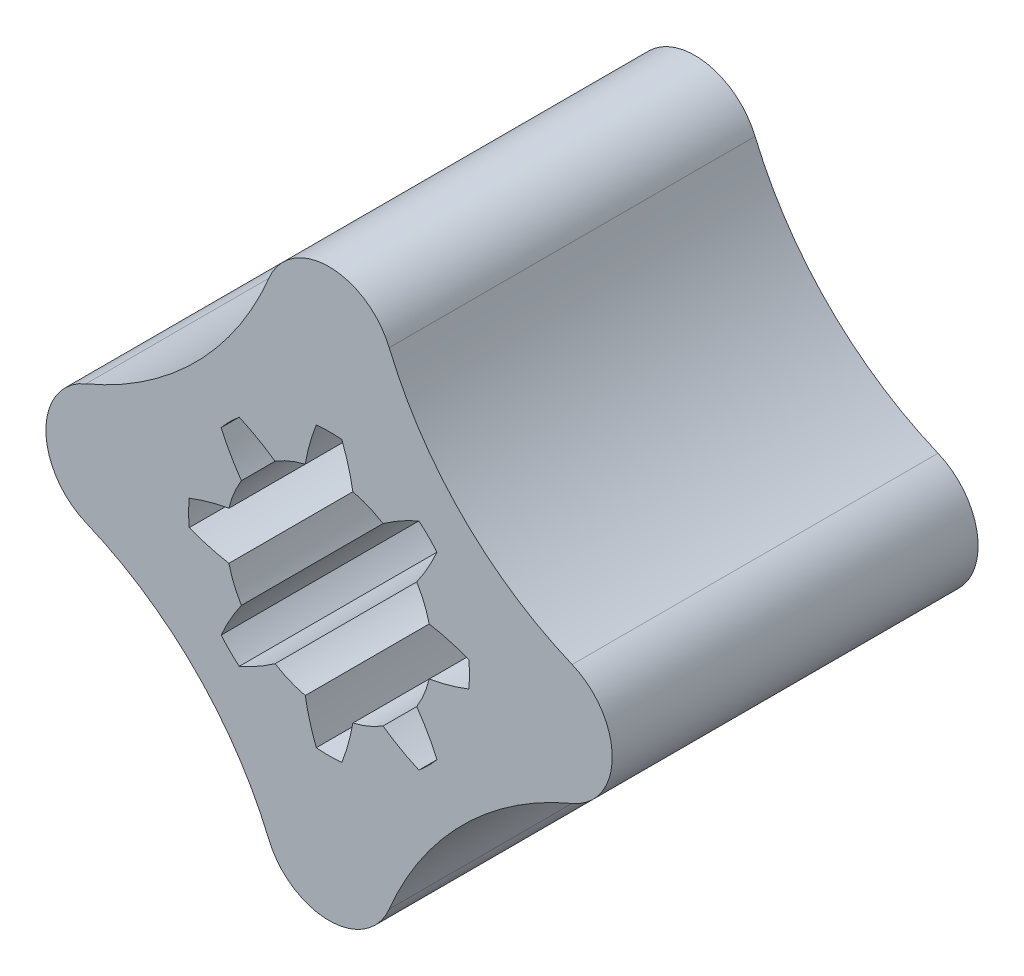
SolidWorks part; units mm, degrees
material "AISI 4140"
ref_plane "Front Plane" through (0, 0, 0) normal (0, 0, 1) x (1, 0, 0)
ref_plane "Top Plane" through (0, 0, 0) normal (0, 1, 0) x (1, 0, 0)
ref_plane "Right Plane" through (0, 0, 0) normal (1, 0, 0) x (0, 0, -1)
sketch "Sketch1" plane through (0, 0, 0) normal (0, 0, 1) x (1, 0, 0)
  line L0 (0, 0) -> (0, 30.3913) construction
  line L1 (0, 0) -> (36.2247, 0) construction
  line L2 (0, 0) -> (30.7829, 0) construction
  line L3 (0, 0) -> (21.991, 21.991) construction
  circle A0 centre (0, 0) radius 16.64 construction
  circle A1 centre (0, 0) radius 11.1 construction
  circle A2 centre (0, 0) radius 6
  arc A3 (3.5352, 14.2851) -> (-3.5352, 14.2851) centre (0, 12.8091) ccw
  arc A4 (14.2851, -3.5352) -> (14.2851, 3.5352) centre (12.8091, 0) ccw
  arc A6 (3.5352, -14.2851) -> (-3.5352, -14.2851) centre (0, -12.8091) cw
  arc A7 (-14.2851, -3.5352) -> (-14.2851, 3.5352) centre (-12.8091, 0) cw
  arc A9 (3.5352, 14.2851) -> (14.2851, 3.5352) centre (21.991, 21.991) ccw
  arc A10 (-3.5352, 14.2851) -> (-14.2851, 3.5352) centre (-21.991, 21.991) cw
  arc A13 (-3.5352, -14.2851) -> (-14.2851, -3.5352) centre (-21.991, -21.991) ccw
  arc A14 (3.5352, -14.2851) -> (14.2851, -3.5352) centre (21.991, -21.991) cw
  dimension "D1" = 22.2
  dimension "D2" = 33.28
  dimension "D3" = 12
  dimension "D6" = 20
  dimension "D7" = 3.8309
  dimension "D4" = 90
  dimension "D5" = 45
extrude "Extrude1" add sketch "Sketch1" along normal blind 21.5
sketch "Sketch4" plane through (0, 0, 0) normal (1, 0, 0) x (0, 0, -1)
  line L0 (0, 0) -> (-35.6112, 0) construction
  line L1 (-21.5, 14.2851) -> (-21.5, 3.5352) construction
  line L3 (0, 0) -> (-21.5, 0)
  line L4 (-7.2, 6.05) -> (-21.5, 6.05)
  line L5 (-5, 8.25) -> (0, 8.25)
  line L6 (-21.5, 6.05) -> (-21.5, 0)
  line L7 (0, 3.5352) -> (0, 14.2851) construction
  line L9 (0, 8.25) -> (0, 0)
  line L10 (-7.2, 6.05) -> (-5, 8.25)
  line L11 (-21.5, 3.5352) -> (-21.5, -3.5352) construction
  dimension "D1" = 16.5
  dimension "D2" = 5
  dimension "D3" = 45
  dimension "D4" = 12.1
revolve "Cut-Revolve1" cut sketch "Sketch4" angle 360 about L0
sketch "Sketch2" plane through (0, 0, 0) normal (0, 0, -1) x (-1, 0, 0)
  line L0 (0, 0) -> (32.9156, 0) construction
  line L1 (0, 0) -> (0, 28.3412) construction
  arc A0 (0.75, 8.2158) -> (-0.75, 8.2158) centre (0, 0) ccw
  arc A1 (-0.75, 8.2158) -> (-1.4, 5.8858) centre (10.4622, 3.8323) ccw
  arc A3 (0.75, 8.2158) -> (1.4, 5.8858) centre (-10.4622, 3.8323) cw
  arc A4 (1.4, 5.8858) -> (-1.4, 5.8858) centre (0, 0) ccw
  circle A7 centre (0, 0) radius 6.05 construction
  dimension "D1" = 16.5
  dimension "D4" = 12.0386
  dimension "D2" = 1.5
  dimension "D3" = 2.8
extrude "Extrude2" cut sketch "Sketch2" against normal up to next
pattern_circular "CirPattern1" count 8 over 360 about axis through (0, 0, 0) along (0, 0, -1) of "Extrude2"
